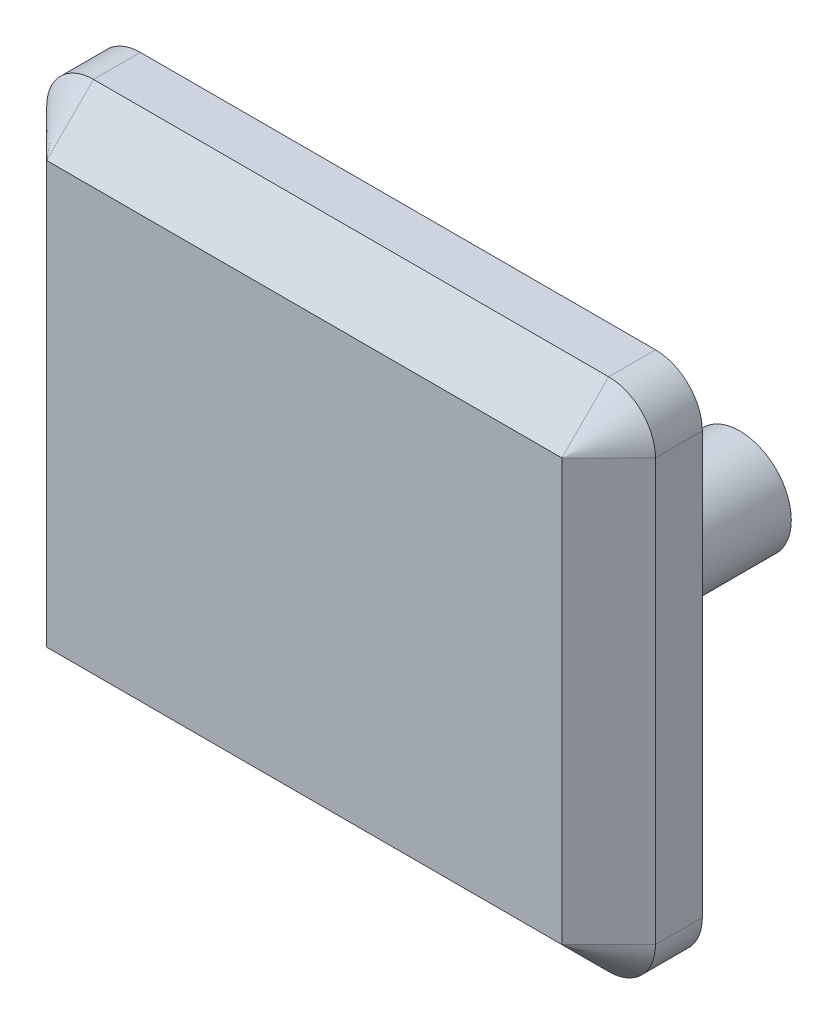
SolidWorks part; units mm, degrees
ref_plane "前视基准面" through (0, 0, 0) normal (0, 0, 1) x (1, 0, 0)
ref_plane "上视基准面" through (0, 0, 0) normal (0, 1, 0) x (1, 0, 0)
ref_plane "右视基准面" through (0, 0, 0) normal (1, 0, 0) x (0, 0, -1)
other "Configuration Table"
sketch "草图1" plane through (0, 0, 0) normal (0, 0, 1) x (1, 0, 0)
  line L1 (-7.2376, 4.5944) -> (-12.7376, 4.5944)
  line L2 (-6.7376, 5.0944) -> (-6.7376, 9.5944)
  line L3 (-7.2376, 10.0944) -> (-12.7376, 10.0944)
  line L4 (-13.2376, 5.0944) -> (-13.2376, 9.5944)
  arc A0 (-6.7376, 9.5944) -> (-7.2376, 10.0944) centre (-7.2376, 9.5944) ccw
  arc A1 (-12.7376, 10.0944) -> (-13.2376, 9.5944) centre (-12.7376, 9.5944) ccw
  arc A2 (-12.7376, 4.5944) -> (-13.2376, 5.0944) centre (-12.7376, 5.0944) cw
  arc A3 (-7.2376, 4.5944) -> (-6.7376, 5.0944) centre (-7.2376, 5.0944) ccw
  point P10 (-13.2376, 10.0944)
  point P13 (-13.2376, 4.5944)
  point P16 (-6.7376, 4.5944)
  dimension "D3" = 0.5
  dimension "D1" = 6.5
  dimension "D2" = 5.5
extrude "凸台-拉伸1" add sketch "草图1" along normal blind 1
chamfer "倒角1" distance 0.5 angle 45 8 edges at (-9.9876, 10.0944, 1) (-13.0912, 9.9479, 1) (-6.8841, 9.9479, 1) (-13.2376, 7.3444, 1) (-6.7376, 7.3444, 1) (-13.0912, 4.7408, 1) (-6.8841, 4.7408, 1) (-9.9876, 4.5944, 1)
sketch "草图2" plane through (0, 0, 0) normal (0, 0, -1) x (-1, 0, 0)
  circle A0 centre (11.7376, 7.3444) radius 0.55
  circle A1 centre (8.2376, 7.3444) radius 0.55
  dimension "D1" = 1.1
extrude "凸台-拉伸2" add sketch "草图2" along normal blind 1.9
